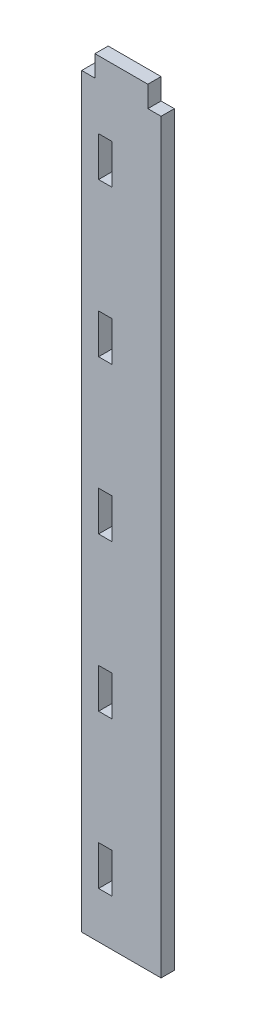
SolidWorks part; units mm, degrees
ref_plane "Plan de face" through (0, 0, 0) normal (0, 0, 1) x (1, 0, 0)
ref_plane "Plan de dessus" through (0, 0, 0) normal (0, 1, 0) x (1, 0, 0)
ref_plane "Plan de droite" through (0, 0, 0) normal (1, 0, 0) x (0, 0, -1)
sketch "Esquisse1" plane through (0, 0, 0) normal (0, 0, 1) x (1, 0, 0)
  line L1 (0, 0) -> (-30, 0)
  line L2 (0, 0) -> (0, 290)
  line L3 (0, 290) -> (-30, 290)
  line L4 (-30, 0) -> (-30, 290)
  line L5 (-23.61, 17.5) -> (-18.61, 17.5)
  line L6 (-23.61, 17.5) -> (-23.61, 32.5)
  line L7 (-23.61, 32.5) -> (-18.61, 32.5)
  line L8 (-18.61, 17.5) -> (-18.61, 32.5)
  line L9 (-23.61, 75.5) -> (-18.61, 75.5)
  line L10 (-23.61, 75.5) -> (-23.61, 90.5)
  line L11 (-23.61, 90.5) -> (-18.61, 90.5)
  line L12 (-18.61, 75.5) -> (-18.61, 90.5)
  line L13 (-23.61, 133.5) -> (-18.61, 133.5)
  line L14 (-23.61, 133.5) -> (-23.61, 148.5)
  line L15 (-23.61, 148.5) -> (-18.61, 148.5)
  line L16 (-18.61, 133.5) -> (-18.61, 148.5)
  line L17 (-23.61, 191.5) -> (-18.61, 191.5)
  line L18 (-23.61, 191.5) -> (-23.61, 206.5)
  line L19 (-23.61, 206.5) -> (-18.61, 206.5)
  line L20 (-18.61, 191.5) -> (-18.61, 206.5)
  line L21 (-23.61, 249.5) -> (-18.61, 249.5)
  line L22 (-23.61, 249.5) -> (-23.61, 264.5)
  line L23 (-23.61, 264.5) -> (-18.61, 264.5)
  line L24 (-18.61, 249.5) -> (-18.61, 264.5)
  line L25 (-30, 290) -> (-25, 290)
  line L26 (-30, 290) -> (-30, 282)
  line L27 (-30, 282) -> (-25, 282)
  line L28 (-25, 290) -> (-25, 282)
  line L29 (0, 290) -> (-5, 290)
  line L30 (0, 290) -> (0, 282)
  line L31 (0, 282) -> (-5, 282)
  line L32 (-5, 290) -> (-5, 282)
  dimension "D1" = 290
  dimension "D2" = 30
  dimension "D3" = 6.39
  dimension "D4" = 15
  dimension "D5" = 17.5
  dimension "D6" = 43
  dimension "D7" = 15
  dimension "D8" = 43
  dimension "D9" = 5
  dimension "D10" = 5
  dimension "D11" = 5
  dimension "D12" = 15
  dimension "D13" = 15
  dimension "D14" = 5
  dimension "D15" = 43
  dimension "D16" = 43
  dimension "D17" = 15
  dimension "D18" = 5
  dimension "D19" = 8
  dimension "D20" = 8
  dimension "D21" = 5
  dimension "D22" = 5
extrude "Boss.-Extru.1" add sketch "Esquisse1" along normal blind 5 contours L3 L4 L1 L2
extrude "Enlèv. mat.-Extru.1" cut sketch "Esquisse1<6>" along normal blind 5 contours L29 L32 L31 L30
sketch "Esquisse1<6>" plane through (0, 0, 0) normal (0, 0, 1) x (1, 0, 0) same geometry as "Esquisse1"
extrude "Enlèv. mat.-Extru.2" cut sketch "Esquisse1<7>" along normal blind 5 contours L25 L28 L27 L26 | L24 L23 L22 L21 | L20 L19 L18 L17 | L16 L15 L14 L13 | L12 L11 L10 L9 | L8 L7 L6 L5
sketch "Esquisse1<7>" plane through (0, 0, 0) normal (0, 0, 1) x (1, 0, 0) same geometry as "Esquisse1"
